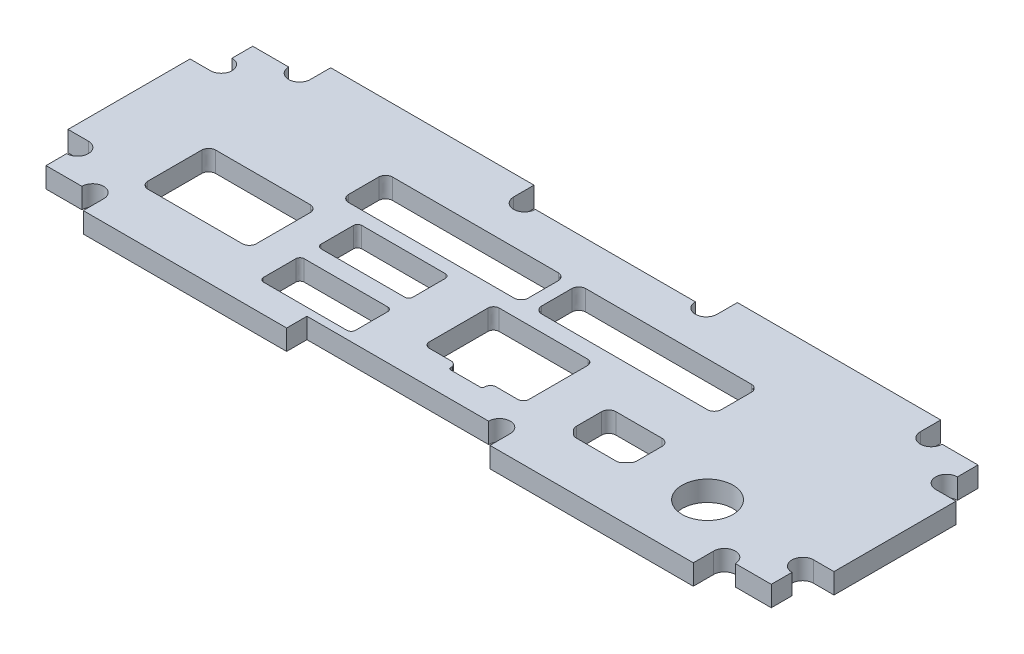
SolidWorks part; units mm, degrees
material "轻木"
ref_plane "Front" through (0, 0, 0) normal (0, 0, 1) x (1, 0, 0)
ref_plane "Top" through (0, 0, 0) normal (0, 1, 0) x (1, 0, 0)
ref_plane "Right" through (0, 0, 0) normal (1, 0, 0) x (0, 0, -1)
sketch "草图1" plane through (0, 0, 0) normal (0, 1, 0) x (1, 0, 0)
  line L0 (49.5, -15.2) -> (49.5, 26.6)
  line L1 (49.5, -15.2) -> (-49.5, -15.2)
  line L2 (-49.5, 26.6) -> (-49.5, -15.2)
  line L3 (-49.5, 26.6) -> (49.5, 26.6)
  line L4 (26.5, 25.2) -> (2, 25.2)
  line L5 (1, 24.2) -> (1, 19.7)
  line L6 (2, 18.7) -> (26.5, 18.7)
  line L7 (27.5, 19.7) -> (27.5, 24.2)
  line L8 (-2, 25.2) -> (-26.5, 25.2)
  line L9 (-27.5, 24.2) -> (-27.5, 19.7)
  line L10 (-26.5, 18.7) -> (-2, 18.7)
  line L11 (-1, 19.7) -> (-1, 24.2)
  line L12 (27.0425, 5.7075) -> (27.5175, 6.1825)
  line L13 (27.825, 6.925) -> (27.825, 10.65)
  line L14 (26.775, 11.7) -> (19.975, 11.7)
  line L15 (18.925, 10.65) -> (18.925, 6.925)
  line L16 (19.2325, 6.1825) -> (19.7075, 5.7075)
  line L17 (20.45, 5.4) -> (26.3, 5.4)
  line L18 (-28, 6.6) -> (-28, 14.6)
  line L19 (-29, 15.6) -> (-43, 15.6)
  line L20 (-44, 14.6) -> (-44, 6.6)
  line L21 (-43, 5.6) -> (-29, 5.6)
  line L22 (-22.575, 10.75) -> (-10.225, 10.75)
  line L23 (-9.625, 11.35) -> (-9.625, 16.15)
  line L24 (-10.225, 16.75) -> (-22.575, 16.75)
  line L25 (-23.175, 16.15) -> (-23.175, 11.35)
  line L26 (-22.575, 2.25) -> (-10.225, 2.25)
  line L27 (-9.625, 2.85) -> (-9.625, 7.65)
  line L28 (-10.225, 8.25) -> (-22.575, 8.25)
  line L29 (-23.175, 7.65) -> (-23.175, 2.85)
  line L30 (2.45, 4.83) -> (6.85, 4.83)
  line L31 (7.15, 5.23) -> (7.15, 5.13)
  line L32 (7.95, 6.03) -> (11.2, 6.03)
  line L33 (12, 6.83) -> (12, 15.53)
  line L34 (11.2, 16.33) -> (-1.9, 16.33)
  line L35 (-2.7, 15.53) -> (-2.7, 6.83)
  line L36 (-1.9, 6.03) -> (1.35, 6.03)
  line L37 (2.15, 5.13) -> (2.15, 5.23)
  circle A0 centre (38, 7.2) radius 3.25
  arc A1 (27.825, 10.65) -> (26.775, 11.7) centre (26.775, 10.65) ccw
  arc A2 (19.975, 11.7) -> (18.925, 10.65) centre (19.975, 10.65) ccw
  spline S0 degree 3 poles (27.5, 24.2) (27.4995, 24.7087) (27.0115, 25.1995) (26.5, 25.2) knots 0 0 0 0 1 1 1 1
  spline S1 degree 3 poles (2, 25.2) (1.4913, 25.1995) (1.0005, 24.7115) (1, 24.2) knots 0 0 0 0 1 1 1 1
  spline S2 degree 3 poles (1, 19.7) (1.0005, 19.1913) (1.4885, 18.7005) (2, 18.7) knots 0 0 0 0 1 1 1 1
  spline S3 degree 3 poles (26.5, 18.7) (27.0087, 18.7005) (27.4995, 19.1885) (27.5, 19.7) knots 0 0 0 0 1 1 1 1
  spline S4 degree 3 poles (-1, 24.2) (-1.0005, 24.7087) (-1.4885, 25.1995) (-2, 25.2) knots 0 0 0 0 1 1 1 1
  spline S5 degree 3 poles (-26.5, 25.2) (-27.0087, 25.1995) (-27.4995, 24.7115) (-27.5, 24.2) knots 0 0 0 0 1 1 1 1
  spline S6 degree 3 poles (-27.5, 19.7) (-27.4995, 19.1913) (-27.0115, 18.7005) (-26.5, 18.7) knots 0 0 0 0 1 1 1 1
  spline S7 degree 3 poles (-2, 18.7) (-1.4913, 18.7005) (-1.0005, 19.1885) (-1, 19.7) knots 0 0 0 0 1 1 1 1
  spline S8 degree 3 poles (27.5175, 6.1825) (27.7133, 6.3801) (27.8238, 6.6403) (27.825, 6.925) knots 0 0 0 0 1 1 1 1
  spline S9 degree 3 poles (18.925, 6.925) (18.9262, 6.6468) (19.0321, 6.3847) (19.2325, 6.1825) knots 0 0 0 0 1 1 1 1
  spline S10 degree 3 poles (19.7075, 5.7075) (19.9051, 5.5117) (20.1653, 5.4012) (20.45, 5.4) knots 0 0 0 0 1 1 1 1
  spline S11 degree 3 poles (26.3, 5.4) (26.5782, 5.4012) (26.8403, 5.5071) (27.0425, 5.7075) knots 0 0 0 0 1 1 1 1
  spline S12 degree 3 poles (-29, 5.6) (-28.4913, 5.6005) (-28.0005, 6.0885) (-28, 6.6) knots 0 0 0 0 1 1 1 1
  spline S13 degree 3 poles (-28, 14.6) (-28.0005, 15.1087) (-28.4885, 15.5995) (-29, 15.6) knots 0 0 0 0 1 1 1 1
  spline S14 degree 3 poles (-43, 15.6) (-43.5087, 15.5995) (-43.9995, 15.1115) (-44, 14.6) knots 0 0 0 0 1 1 1 1
  spline S15 degree 3 poles (-44, 6.6) (-43.9995, 6.0913) (-43.5115, 5.6005) (-43, 5.6) knots 0 0 0 0 1 1 1 1
  spline S16 degree 3 poles (-23.175, 11.35) (-23.1745, 11.0447) (-22.8831, 10.7505) (-22.575, 10.75) knots 0 0 0 0 1 1 1 1
  spline S17 degree 3 poles (-10.225, 10.75) (-9.9197, 10.7505) (-9.6255, 11.0419) (-9.625, 11.35) knots 0 0 0 0 1 1 1 1
  spline S18 degree 3 poles (-9.625, 16.15) (-9.6255, 16.4553) (-9.9169, 16.7495) (-10.225, 16.75) knots 0 0 0 0 1 1 1 1
  spline S19 degree 3 poles (-22.575, 16.75) (-22.8803, 16.7495) (-23.1745, 16.4581) (-23.175, 16.15) knots 0 0 0 0 1 1 1 1
  spline S20 degree 3 poles (-23.175, 2.85) (-23.1745, 2.5447) (-22.8831, 2.2505) (-22.575, 2.25) knots 0 0 0 0 1 1 1 1
  spline S21 degree 3 poles (-10.225, 2.25) (-9.9197, 2.2505) (-9.6255, 2.5419) (-9.625, 2.85) knots 0 0 0 0 1 1 1 1
  spline S22 degree 3 poles (-9.625, 7.65) (-9.6255, 7.9553) (-9.9169, 8.2495) (-10.225, 8.25) knots 0 0 0 0 1 1 1 1
  spline S23 degree 3 poles (-22.575, 8.25) (-22.8803, 8.2495) (-23.1745, 7.9581) (-23.175, 7.65) knots 0 0 0 0 1 1 1 1
  spline S24 degree 3 poles (6.85, 4.83) (7.0149, 4.8313) (7.1487, 4.9677) (7.15, 5.13) knots 0 0 0 0 1 1 1 1
  spline S25 degree 3 poles (7.95, 6.03) (7.5311, 6.03) (7.15, 5.6489) (7.15, 5.23) knots 0 0 0 0 1 1 1 1
  spline S26 degree 3 poles (11.2, 6.03) (11.607, 6.0305) (11.9995, 6.4202) (12, 6.83) knots 0 0 0 0 1 1 1 1
  spline S27 degree 3 poles (12, 15.53) (11.9995, 15.937) (11.6098, 16.3295) (11.2, 16.33) knots 0 0 0 0 1 1 1 1
  spline S28 degree 3 poles (-1.9, 16.33) (-2.307, 16.3295) (-2.6995, 15.9398) (-2.7, 15.53) knots 0 0 0 0 1 1 1 1
  spline S29 degree 3 poles (-2.7, 6.83) (-2.6995, 6.423) (-2.3098, 6.0305) (-1.9, 6.03) knots 0 0 0 0 1 1 1 1
  spline S30 degree 3 poles (2.15, 5.23) (2.15, 5.6489) (1.7689, 6.03) (1.35, 6.03) knots 0 0 0 0 1 1 1 1
  spline S31 degree 3 poles (2.15, 5.13) (2.1513, 4.9651) (2.2877, 4.8313) (2.45, 4.83) knots 0 0 0 0 1 1 1 1
extrude "凸台-拉伸1" add sketch "草图1" along normal mid plane 3
sketch "草图2" plane through (0, -1.5, 0) normal (0, -1, 0) x (1, 0, 0)
  line L0 (49.5, 15.2) -> (49.5, -26.6) construction
  line L1 (-49.5, 15.2) -> (49.5, 15.2)
  line L2 (-49.5, 15.2) -> (-49.5, -1.1)
  line L3 (-49.5, -1.1) -> (49.5, -1.1)
  line L4 (49.5, 15.2) -> (49.5, -1.1)
  line L5 (-49.5, 15.2) -> (49.5, -1.1) construction
  line L6 (-49.5, -1.1) -> (49.5, 15.2) construction
  point P4 (0, 7.05)
  dimension "D1" = 16.3
extrude "切除-拉伸1" cut sketch "草图2" against normal blind 10
sketch "草图6" plane through (0, 0, -26.6) normal (0, 0, -1) x (-1, 0, 0)
  line L4 (-49.5, -1.5) -> (49.5, -1.5)
  line L5 (49.5, -1.5) -> (49.5, 1.5)
  line L6 (49.5, 1.5) -> (-49.5, 1.5)
  line L7 (-49.5, 1.5) -> (-49.5, -1.5)
  line L8 (-49.5, -1.5) -> (49.5, -1.5)
  line L9 (49.5, -1.5) -> (49.5, 1.5)
  line L10 (49.5, 1.5) -> (-49.5, 1.5)
  line L11 (-49.5, 1.5) -> (-49.5, -1.5)
  dimension "D1" = 0
extrude "凸台-拉伸4" add sketch "草图6" along normal blind 5
sketch "草图3" plane through (0, 0, -1.1) normal (0, 0, 1) x (1, 0, 0)
  line L0 (0, 1.5) -> (0, -10.5667) construction
  line L1 (49.5, 1.5) -> (-49.5, 1.5) construction
  line L2 (45, 1.5) -> (15, 1.5)
  line L3 (-45, -1.5) -> (-15, -1.5)
  line L4 (-45, -1.5) -> (-45, 1.5)
  line L5 (-45, 1.5) -> (-15, 1.5)
  line L6 (-15, -1.5) -> (-15, 1.5)
  line L7 (-30, 1.5) -> (-30, -1.5) construction
  line L8 (-45, 0) -> (-15, 0) construction
  line L9 (15, -1.5) -> (15, 1.5)
  line L10 (45, -1.5) -> (15, -1.5)
  line L11 (45, -1.5) -> (45, 1.5)
  point P5 (-30, 0)
  dimension "D1" = 15
  dimension "D2" = 30
  dimension "D3" = 3
extrude "凸台-拉伸2" add sketch "草图3" along normal blind 3
ref_plane "基准面1" through (0, 0, -16.35) normal (0, 0, 1) x (1, 0, 0)
mirror "镜向1" about plane through (0, 0, -16.35) normal (0, 0, 1) of "凸台-拉伸2"
sketch "草图5" plane through (0, 1.5, 0) normal (0, 1, 0) x (1, 0, 0)
  line L0 (0, 0) -> (0, 40.6631) construction
  line L1 (-49.5, 31.6) -> (-53.5, 31.6)
  line L2 (-49.5, 31.6) -> (-49.5, 1.1)
  line L3 (-49.5, 1.1) -> (-53.5, 1.1)
  line L4 (-53.5, 31.6) -> (-53.5, 1.1)
  line L5 (-49.5, 31.6) -> (-53.5, 1.1) construction
  line L6 (-49.5, 1.1) -> (-53.5, 31.6) construction
  line L8 (-53.5, 16.35) -> (-69.1581, 16.35) construction
  line L11 (-56.5, 25.35) -> (-56.5, 7.35)
  line L12 (-56.5, 7.35) -> (-53.5, 7.35)
  line L13 (-56.5, 25.35) -> (-53.5, 25.35)
  line L14 (49.5, 1.1) -> (53.5, 31.6) construction
  line L15 (49.5, 31.6) -> (53.5, 1.1) construction
  line L16 (56.5, 25.35) -> (53.5, 25.35)
  line L17 (56.5, 7.35) -> (53.5, 7.35)
  line L18 (56.5, 25.35) -> (56.5, 7.35)
  line L19 (53.5, 31.6) -> (53.5, 1.1)
  line L20 (49.5, 1.1) -> (53.5, 1.1)
  line L21 (49.5, 31.6) -> (49.5, 1.1)
  line L22 (49.5, 31.6) -> (53.5, 31.6)
  point P4 (-51.5, 16.35)
  point P17 (-56.5, 16.35)
  point P21 (-56.5, 25.35)
  point P28 (56.5, 16.35)
  point P29 (51.5, 16.35)
  dimension "D1" = 3
  dimension "D2" = 4
  dimension "D3" = 18
extrude "凸台-拉伸3" add sketch "草图5" against normal blind 3 contours L13 L11 L12 L4 | L1 L4 L3 L2 | L22 L21 L20 L19 | L16 L19 L17 L18 region at (-51.5, 1.5, -16.35) region at (-55, 1.5, -16.35) region at (55, 1.5, -16.35) region at (51.5, 1.5, -16.35)
sketch "草图4" plane through (0, 1.5, 0) normal (0, 1, 0) x (1, 0, 0)
  line L2 (-45, 1.1) -> (-53.5, 1.1) construction
  line L3 (15, 1.1) -> (-15, 1.1) construction
  line L5 (53.5, 1.1) -> (45, 1.1) construction
  line L6 (-53.5, 31.6) -> (-53.5, 25.35) construction
  line L7 (-53.5, 7.35) -> (-53.5, 1.1) construction
  line L8 (53.5, 7.35) -> (53.5, 1.1) construction
  line L9 (53.5, 31.6) -> (53.5, 25.35) construction
  line L10 (-53.5, 31.6) -> (-45, 31.6) construction
  line L11 (-15, 31.6) -> (15, 31.6) construction
  line L12 (45, 31.6) -> (49.5, 31.6) construction
  circle A2 centre (-46.6, 1.1) radius 1.6
  circle A4 centre (13.4, 1.1) radius 1.6
  circle A7 centre (46.6, 1.1) radius 1.6
  circle A8 centre (-53.5, 26.95) radius 1.6
  circle A9 centre (-53.5, 5.75) radius 1.6
  circle A10 centre (53.5, 5.75) radius 1.6
  circle A11 centre (53.5, 26.95) radius 1.6
  circle A12 centre (-46.6, 31.6) radius 1.6
  circle A13 centre (-13.4, 31.6) radius 1.6
  circle A14 centre (13.4, 31.6) radius 1.6
  circle A15 centre (46.6, 31.6) radius 1.6
  dimension "D1" = 3.2
extrude "切除-拉伸2" cut sketch "草图4" against normal blind 3
sketch "草图8" plane through (0, 1.5, 0) normal (0, 1, 0) x (1, 0, 0)
  circle A0 centre (38, 7.2) radius 3.25 construction
  circle A1 centre (38, 7.2) radius 3.25
  circle A2 centre (38, 7.2) radius 3.75
  dimension "D1" = 0.5
extrude "切除-拉伸3" cut sketch "草图8" against normal blind 10
